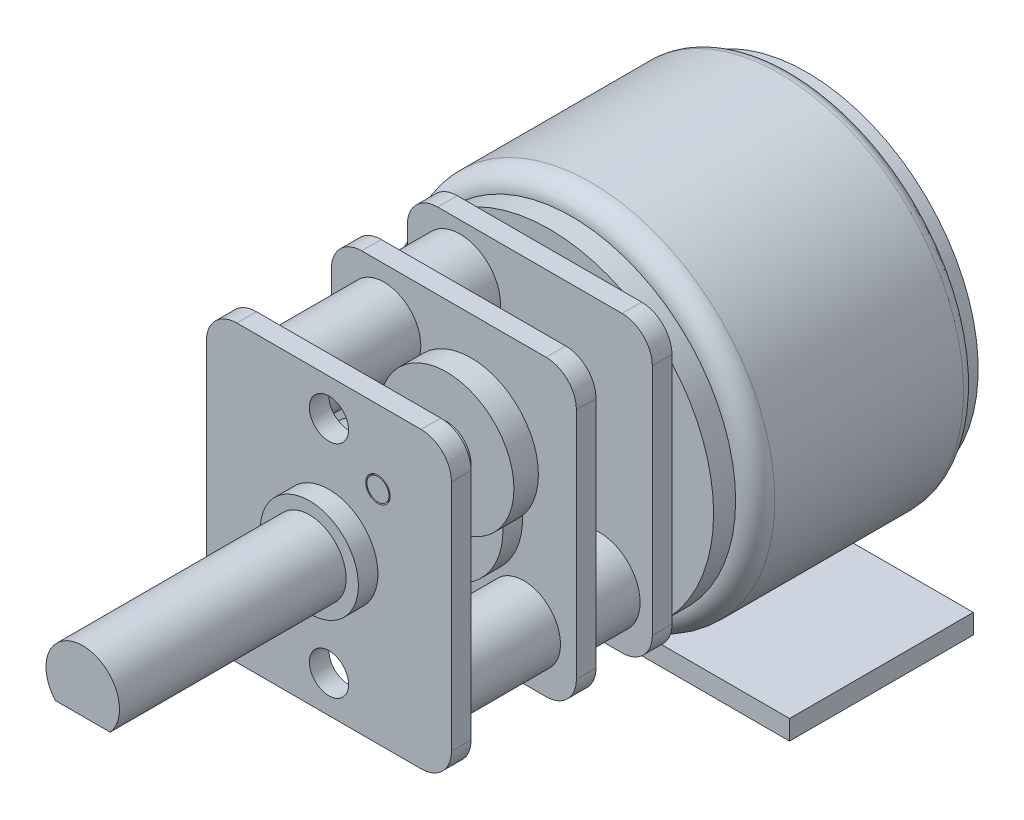
SolidWorks part; units mm, degrees
ref_plane "Front" through (0, 0, 0) normal (0, 0, 1) x (1, 0, 0)
ref_plane "Top" through (0, 0, 0) normal (0, 1, 0) x (1, 0, 0)
ref_plane "Right" through (0, 0, 0) normal (1, 0, 0) x (0, 0, -1)
sketch "Эскиз1" plane through (0, 0, 0) normal (0, 1, 0) x (1, 0, 0)
  line L0 (0, 0) -> (0, -39.2335) construction
  line L1 (0, 0) -> (-0.5, 0)
  line L3 (-0.75, -0.5) -> (-3, -0.5)
  line L4 (-3, -0.5) -> (-3, -1.5)
  line L5 (-3, -1.5) -> (-7, -1.5)
  line L6 (-7, -1.5) -> (-7, -2.1)
  line L8 (-7.5, -2.6) -> (-7.5, -10.3)
  line L10 (-6.7, -11.1) -> (-6.7, -12)
  line L11 (-6.7, -12) -> (-0.75, -12)
  line L12 (0, -12) -> (0, 0)
  line L14 (-7, -2.1) -> (-7, -2.6) construction
  line L15 (-6.7, -11.1) -> (-6.7, -10.3) construction
  line L16 (-6.7, -11.1) -> (-7.5, -11.1) construction
  line L18 (0, -21) -> (-2, -21)
  line L19 (-2, -21) -> (-2, -21.8)
  line L20 (-2, -21.8) -> (-1.5, -21.8)
  line L21 (-1.5, -21.8) -> (-1.5, -31.05)
  line L22 (-1.5, -31.05) -> (0, -31.05)
  line L24 (0, -21) -> (0, -31.05)
  line L25 (-0.75, -12) -> (-0.75, -13.75) construction
  line L26 (0, -14) -> (-0.5, -14) construction
  line L27 (-0.75, -0.5) -> (-0.75, -0.25)
  line L28 (0, -12) -> (-0.75, -12)
  arc A0 (-7, -2.1) -> (-7.5, -2.6) centre (-7, -2.6) ccw
  arc A1 (-7.5, -10.3) -> (-6.7, -11.1) centre (-6.7, -10.3) ccw
  arc A2 (-0.75, -13.75) -> (-0.5, -14) centre (-0.5, -13.75) ccw construction
  arc A3 (-0.5, 0) -> (-0.75, -0.25) centre (-0.5, -0.25) ccw
  dimension "D1" = 6
  dimension "D7" = 0.9
  dimension "D10" = 10.5
  dimension "D16" = 2
  dimension "D4" = 0.5
  dimension "D5" = 0.25
  dimension "D2" = 15
  dimension "D3" = 1
  dimension "D6" = 0.6
  dimension "D8" = 14
  dimension "D9" = 13.4
  dimension "D11" = 19.5
  dimension "D12" = 4
  dimension "D13" = 0.8
  dimension "D14" = 9.25
  dimension "D15" = 3
  dimension "D17" = 1.5
revolve "Motor" add sketch "Эскиз1" angle 360 about L0
sketch "Эскиз2" plane through (0, 0, 31.05) normal (0, 0, 1) x (1, 0, 0)
  line L0 (-1.118, -1) -> (1.118, -1)
  line L1 (-1.6853, 1.5) -> (1.9295, 1.5) construction
  arc A0 (1.118, -1) -> (-1.118, -1) centre (0, 0) ccw
  circle A1 centre (0, 0) radius 1.5 construction
  dimension "D1" = 2.5
extrude "Вырез-Вытянуть2" cut sketch "Эскиз2" against normal up to surface (9.25 mm away) flip side to cut up to face at (-1.5, 0, 21.8)
sketch "Эскиз7" plane through (0, 0, 12) normal (0, 0, 1) x (1, 0, 0)
  line L1 (3.7627, 6) -> (-3.7627, 6)
  line L2 (5, 4.7627) -> (5, -4.7627)
  line L3 (3.7627, -6) -> (-3.7627, -6)
  line L4 (-5, 4.7627) -> (-5, -4.7627)
  line L5 (5, 6) -> (-5, -6) construction
  line L6 (5, -6) -> (-5, 6) construction
  arc A0 (-3.7627, 6) -> (-5, 4.7627) centre (-3.7627, 4.7627) ccw
  arc A1 (-5, -4.7627) -> (-3.7627, -6) centre (-3.7627, -4.7627) ccw
  arc A2 (3.7627, -6) -> (5, -4.7627) centre (3.7627, -4.7627) ccw
  arc A3 (5, 4.7627) -> (3.7627, 6) centre (3.7627, 4.7627) ccw
  point P0 (0, 0)
  point P18 (4.6376, -5.6376)
  point P19 (-4.6376, 5.6376)
  dimension "D3" = 14.6
  dimension "D4" = 1.2373
  dimension "D1" = 10
  dimension "D2" = 12
extrude "Бобышка-Вытянуть5" add sketch "Эскиз7" along normal blind 0.8
sketch "Эскиз8" plane through (0, 0, 21) normal (0, 0, -1) x (-1, 0, 0)
  line L0 (-5, -4.7627) -> (-5, -4.4598) construction
  line L1 (3.7627, 6) -> (-3.7627, 6)
  line L2 (5, 4.7627) -> (5, -4.7627)
  line L3 (3.7627, -6) -> (-3.7627, -6)
  line L4 (-5, 4.7627) -> (-5, -4.7627)
  line L5 (5, 6) -> (-5, -6) construction
  line L6 (5, -6) -> (-5, 6) construction
  line L7 (3.7627, -6) -> (2.9816, -6) construction
  line L8 (0, -4.5) -> (0, 4.5) construction
  line L9 (2, -3) -> (-2, 3) construction
  arc A0 (-3.7627, 6) -> (-5, 4.7627) centre (-3.7627, 4.7627) ccw
  arc A1 (-5, -4.7627) -> (-3.7627, -6) centre (-3.7627, -4.7627) ccw
  arc A2 (3.7627, -6) -> (5, -4.7627) centre (3.7627, -4.7627) ccw
  arc A3 (5, 4.7627) -> (3.7627, 6) centre (3.7627, 4.7627) ccw
  arc A4 (-5, -4.7627) -> (-3.7627, -6) centre (-3.7627, -4.7627) ccw construction
  circle A5 centre (0, -4.5) radius 0.8
  circle A6 centre (0, 4.5) radius 0.8
  circle A8 centre (2, -3) radius 0.5
  circle A9 centre (-2, 3) radius 0.5
  point P0 (0, 0)
  point P35 (2, -3)
  point P36 (-2, 3)
  dimension "D3" = 1
  dimension "D1" = 1.6
  dimension "D2" = 9
  dimension "D4" = 3
  dimension "D5" = 3
extrude "Бобышка-Вытянуть6" add sketch "Эскиз8" along normal blind 0.8
sketch "Эскиз9" plane through (0, 0, 12.8) normal (0, 0, 1) x (1, 0, 0)
  line L0 (4.5, -2.7511) -> (4.5, -4.8531) construction
  line L1 (2.0633, -5.5) -> (3.9242, -5.5) construction
  line L2 (5, -4.7627) -> (5, 4.7627) construction
  line L3 (-3.7627, -6) -> (3.7627, -6) construction
  line L4 (2.85, -3.85) -> (-2.85, 3.85) construction
  circle A0 centre (2.85, -3.85) radius 1.65
  circle A1 centre (-2.85, 3.85) radius 1.65
  point P14 (0, 0)
  dimension "D1" = 3.3
  dimension "D2" = 0.5
  dimension "D3" = 0.5
extrude "Бобышка-Вытянуть7" add sketch "Эскиз9" along normal blind 2.3
sketch "Эскиз10" plane through (0, 0, 15.1) normal (0, 0, 1) x (1, 0, 0)
  line L1 (3.7627, 6) -> (-3.7627, 6)
  line L2 (5, 4.7627) -> (5, -4.7627)
  line L3 (3.7627, -6) -> (1.2373, -6)
  line L4 (-5, 4.7627) -> (-5, -0.2627)
  line L5 (5, 6) -> (-5, -6) construction
  line L6 (5, -6) -> (-5, 6) construction
  line L8 (3.7627, 6) -> (2.9816, 6) construction
  line L9 (5, -4.7627) -> (5, -4.4598) construction
  line L10 (-3.7627, -1.5) -> (-1.2373, -1.5)
  line L11 (0, -4.7627) -> (0, -2.7373)
  arc A0 (-3.7627, 6) -> (-5, 4.7627) centre (-3.7627, 4.7627) ccw
  arc A2 (3.7627, -6) -> (5, -4.7627) centre (3.7627, -4.7627) ccw
  arc A3 (5, 4.7627) -> (3.7627, 6) centre (3.7627, 4.7627) ccw
  arc A4 (5, 4.7627) -> (3.7627, 6) centre (3.7627, 4.7627) ccw construction
  arc A5 (1.2373, -6) -> (0, -4.7627) centre (1.2373, -4.7627) cw
  arc A6 (-5, -0.2627) -> (-3.7627, -1.5) centre (-3.7627, -0.2627) ccw
  arc A7 (0, -2.7373) -> (-1.2373, -1.5) centre (-1.2373, -2.7373) ccw
  point P0 (0, 0)
  dimension "D1" = 5
  dimension "D2" = 7.5
extrude "Бобышка-Вытянуть8" add sketch "Эскиз10" along normal blind 0.8
sketch "Эскиз11" plane through (0, 0, 15.9) normal (0, 0, 1) x (1, 0, 0)
  circle A0 centre (2.85, -3.85) radius 1.5
  circle A1 centre (-2.85, 3.85) radius 1.5
  circle A4 centre (-2.85, 3.85) radius 1.65 construction
  circle A5 centre (2.85, -3.85) radius 1.65 construction
  dimension "D1" = 3
extrude "Бобышка-Вытянуть9" add sketch "Эскиз11" along normal up to next
sketch "Эскиз12" plane through (0, 0, 0) normal (0, 1, 0) x (1, 0, 0)
  line L0 (0, -20.2) -> (0, -12.8) construction
  line L1 (-1.35, -20.2) -> (-4.35, -20.2) construction
  line L2 (-4.5, -12.8) -> (-1.2, -12.8) construction
  line L3 (0, -20.2) -> (-0.5, -20.2)
  line L4 (-0.5, -20.2) -> (-0.5, -20)
  line L5 (-0.5, -20) -> (-3, -20)
  line L6 (-3, -20) -> (-3, -18.6)
  line L7 (-3, -18.6) -> (-0.5, -18.6)
  line L8 (-0.5, -18.6) -> (-0.5, -18.3)
  line L9 (-0.5, -18.3) -> (-1.5, -18.3)
  line L10 (-1.5, -18.3) -> (-1.5, -16.9)
  line L13 (-1.5, -16.9) -> (-3, -16.9)
  line L14 (-3, -16.9) -> (-3, -16.1)
  line L15 (-3, -16.1) -> (-0.5, -16.1)
  line L16 (-0.5, -16.1) -> (-0.5, -15.9)
  line L17 (-0.5, -15.9) -> (0, -15.9)
  line L18 (0, -15.9) -> (0, -20.2)
  line L19 (-4.35, -15.9) -> (-1.35, -15.9) construction
  line L21 (0, -12.8) -> (-0.75, -12.8)
  line L22 (-0.75, -12.8) -> (-0.75, -13)
  line L23 (-0.75, -13) -> (-1.5, -13)
  line L24 (-1.5, -13) -> (-1.5, -14)
  line L25 (-1.5, -14) -> (-0.75, -14)
  line L26 (-0.75, -14) -> (-0.75, -14.15)
  line L27 (-0.5, -14.4) -> (0, -14.4)
  line L28 (0, -14.4) -> (0, -12.8)
  arc A0 (-0.75, -14.15) -> (-0.5, -14.4) centre (-0.5, -14.15) ccw
  dimension "D8" = 1.5
  dimension "D10" = 0.25
  dimension "D1" = 1
  dimension "D2" = 0.2
  dimension "D3" = 1.4
  dimension "D4" = 0.8
  dimension "D5" = 1.4
  dimension "D6" = 3
  dimension "D7" = 6
  dimension "D9" = 1
  dimension "D11" = 3
  dimension "D12" = 1.6
revolve "Повернуть1" add sketch "Эскиз12" angle 360 about L0
ref_plane "Плоскость2" through (0, 0, 0) normal (-0.8321, 0.5547, 0) x (0, 0, 1)
sketch "Эскиз13" plane through (0, 0, 0) normal (-0.8321, 0.5547, 0) x (0, 0, 1)
  line L0 (21, -3.6056) -> (12.8, -3.6056)
  line L1 (12.8, -0.75) -> (12.8, 0.75) construction
  line L2 (21, -3.6056) -> (21, -3.1556)
  line L3 (21, -3.1556) -> (17.3, -3.1556)
  line L4 (17.3, -3.1556) -> (17.3, -2.6056)
  line L5 (17.3, -2.6056) -> (14, -2.6056)
  line L6 (14, -2.6056) -> (14, -0.8556)
  line L7 (14, -0.8556) -> (13, -0.8556)
  line L8 (13, -0.8556) -> (13, -3.305)
  line L9 (13, -3.305) -> (12.8, -3.305)
  line L10 (12.8, -3.305) -> (12.8, -3.6056)
  line L12 (21, -3.6056) -> (22.843, -3.6056) construction
  dimension "D1" = 0.9
  dimension "D2" = 2
  dimension "D3" = 5.5
  dimension "D4" = 0.2
  dimension "D5" = 1
  dimension "D6" = 3.3
revolve "Повернуть2" add sketch "Эскиз13" angle 360 about L12
sketch "Эскиз14" plane through (0, 0, 0) normal (-0.8321, 0.5547, 0) x (0, 0, 1)
  line L0 (21, 3.6056) -> (15.9, 3.6056)
  line L1 (15.9, -0.5) -> (15.9, 0.5) construction
  line L2 (21, 3.6056) -> (21.7209, 3.6056) construction
  line L3 (21, 3.6056) -> (21, 3.1556)
  line L4 (21, 3.1556) -> (20, 3.1556)
  line L5 (20, 3.1556) -> (20, 2.6056)
  line L6 (20, 2.6056) -> (18.2, 2.6056)
  line L7 (18.2, 2.6056) -> (18.2, 0.8556)
  line L8 (18.2, 0.8556) -> (17.2, 0.8556)
  line L9 (17.2, 0.8556) -> (17.2, 3.1056)
  line L10 (17.2, 3.1056) -> (15.9, 3.1056)
  line L11 (15.9, 3.1056) -> (15.9, 3.6056)
  line L12 (20.2, 6.7363) -> (20.2, -1.1893) construction
  line L13 (15.9, -1.1893) -> (15.9, 6.7363) construction
  dimension "D1" = 0.9
  dimension "D2" = 1
  dimension "D3" = 2
  dimension "D4" = 5.5
  dimension "D5" = 0.2
  dimension "D6" = 2
  dimension "D7" = 1.3
revolve "Повернуть3" add sketch "Эскиз14" angle 360 about L2
ref_plane "Плоскость1" through (0, -7.5, 0) normal (0, -1, 0) x (-1, 0, 0)
sketch "Эскиз4" plane through (0, -7.5, 0) normal (0, -1, 0) x (-1, 0, 0)
  line L0 (0, -2.6) -> (0, -10.3) construction
  line L1 (3.5, -10.2) -> (-8, -10.2)
  line L2 (3.5, -10.2) -> (3.5, -2.7)
  line L3 (3.5, -2.7) -> (-8, -2.7)
  line L4 (-8, -10.2) -> (-8, -2.7)
  line L5 (3.5, -6.45) -> (-8, -6.45) construction
  line L7 (7.5, -10.3) -> (-7.5, -10.3) construction
  line L8 (7.5, -2.6) -> (-7.5, -2.6) construction
  point P5 (0, -6.45)
  dimension "D1" = 7.5
  dimension "D2" = 11.5
  dimension "D3" = 3.5
extrude "Плата" add sketch "Эскиз4" along normal blind 0.8 separate body
sketch "Пайка контактов" plane through (0, -8.3, 0) normal (0, -1, 0) x (1, 0, 0)
  line L0 (-0.75, 7.2) -> (2.25, 7.2) construction
  line L1 (0.75, 5.7) -> (-2.25, 5.7) construction
  line L2 (-0.75, 5.7) -> (-0.75, 7.2) construction
  line L3 (-0.75, 6.45) -> (-3.5, 6.45) construction
  line L4 (-3.5, 10.2) -> (-3.5, 2.7) construction
  line L5 (-0.75, 7.2) -> (0.75, 5.7) construction
  line L6 (0, 6.45) -> (0, 0) construction
  line L8 (7, 5.5333) -> (7, 3.7) construction
  line L9 (7, 7.3667) -> (7, 5.5333) construction
  line L10 (7, 7.3667) -> (7, 9.2) construction
  line L11 (7, 6.45) -> (8, 6.45) construction
  line L12 (8, 2.7) -> (8, 10.2) construction
  circle A0 centre (-2.25, 5.7) radius 0.75
  circle A1 centre (-0.75, 7.2) radius 0.75
  circle A2 centre (0.75, 5.7) radius 0.75
  circle A3 centre (2.25, 7.2) radius 0.75
  circle A4 centre (7, 3.7) radius 0.75
  circle A5 centre (7, 5.5333) radius 0.75
  circle A6 centre (7, 7.3667) radius 0.75
  circle A7 centre (7, 9.2) radius 0.75
  point P14 (-3.5, 6.45)
  point P29 (8, 6.45)
  dimension "D1" = 1.5
  dimension "D4" = 1.5
  dimension "D2" = 3
  dimension "D3" = 1.5
  dimension "D5" = 5.5
  dimension "D6" = 1
extrude "Бобышка-Вытянуть3" add sketch "Пайка контактов" along normal blind 0.7 draft 35
sketch "Эскиз6" plane through (0, -8.3, 0) normal (0, -1, 0) x (1, 0, 0)
  line L0 (5.7717, 10.2) -> (5.7717, 2.7) construction
  line L1 (8, 10.2) -> (-3.5, 10.2) construction
  line L2 (-3.5, 2.7) -> (8, 2.7) construction
  line L3 (-3.5, 8.1932) -> (8, 8.1932) construction
  line L4 (-3.5, 10.2) -> (-3.5, 2.7) construction
  line L5 (8, 2.7) -> (8, 10.2) construction
  text T0 "B1 B2 A1 A2" font "Century Gothic" height 0.85
  text T1 " B1 A2 B2 A1" font "Century Gothic" height 0.8
extrude "Бобышка-Вытянуть4" add sketch "Эскиз6" along normal blind 0.01
